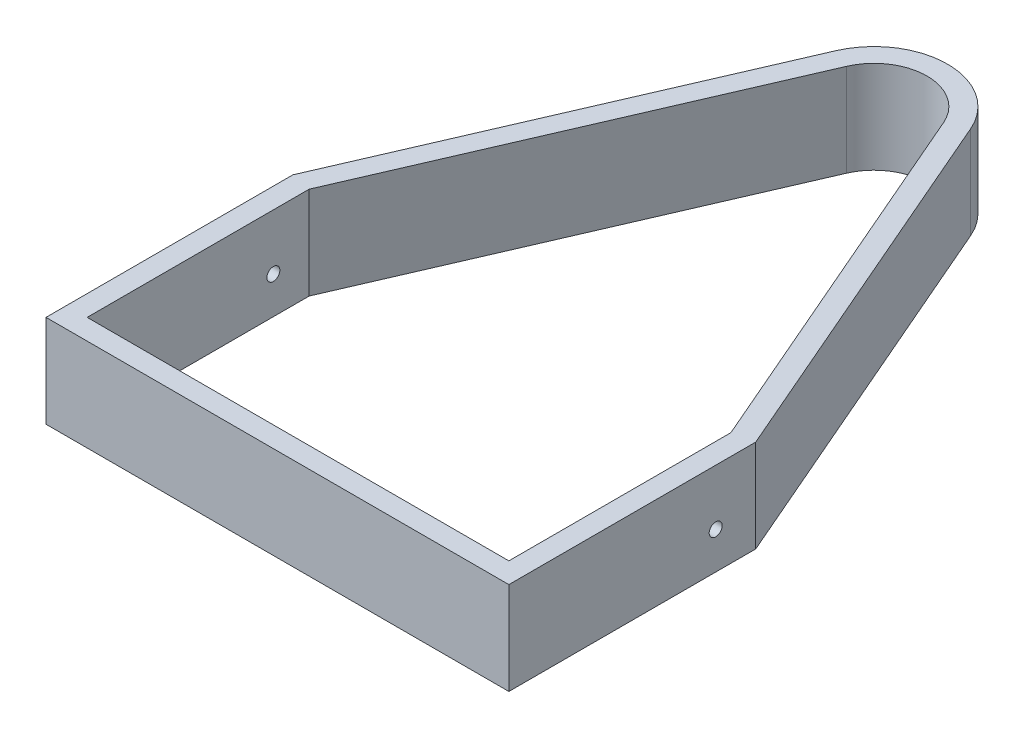
SolidWorks part; units mm, degrees
ref_plane "Front Plane" through (0, 0, 0) normal (0, 0, 1) x (1, 0, 0)
ref_plane "Top Plane" through (0, 0, 0) normal (0, 1, 0) x (1, 0, 0)
ref_plane "Right Plane" through (0, 0, 0) normal (1, 0, 0) x (0, 0, -1)
sketch "Sketch1" plane through (0, 0, 0) normal (0, 1, 0) x (1, 0, 0)
  line L0 (-71.4375, 0) -> (71.4375, 0)
  line L1 (-71.4375, 19.05) -> (71.4375, 19.05) construction
  line L2 (-71.4375, 0) -> (-71.4375, 76.2)
  line L3 (-71.4375, 19.05) -> (0, 184.15) construction
  line L8 (0, 184.15) -> (71.4375, 19.05) construction
  line L13 (71.4375, 0) -> (71.4375, 76.2)
  line L14 (-71.4375, 76.2) -> (-20.8288, 193.1624)
  line L15 (20.8288, 193.1624) -> (71.4375, 76.2)
  line L16 (-65.0875, 6.35) -> (-65.0875, 74.8851)
  line L17 (-65.0875, 74.8851) -> (-15.0009, 190.6408)
  line L18 (15.0009, 190.6408) -> (65.0875, 74.8851)
  line L19 (65.0875, 6.35) -> (65.0875, 74.8851)
  line L20 (-65.0875, 6.35) -> (65.0875, 6.35)
  arc A0 (-20.8288, 193.1624) -> (20.8288, 193.1624) centre (0, 184.15) cw
  arc A2 (-15.0009, 190.6408) -> (15.0009, 190.6408) centre (0, 184.15) cw
  point P4 (0, 0)
  dimension "D1" = 142.875
  dimension "D2" = 165.1
  dimension "D3" = 19.05
  dimension "D4" = 76.2
  dimension "D6" = 6.35
extrude "Boss-Extrude1" add sketch "Sketch1" along normal blind 28.575
sketch "Sketch2" plane through (0, 0, 0) normal (1, 0, 0) x (0, 0, -1)
  line L4 (74.8851, 28.575) -> (74.8851, 0) construction
  line L5 (0, 0) -> (76.2, 0) construction
  circle A0 centre (63.8361, 11.43) radius 11.049 construction
  circle A1 centre (63.8361, 11.43) radius 2
  dimension "D1" = 22.098
  dimension "D2" = 4
  dimension "D3" = 11.43
extrude "Cut-Extrude1" cut sketch "Sketch2" against normal up to next from surface starting at face at (-65.0875, 14.2875, -40.6176)
extrude "Cut-Extrude3" cut sketch "Sketch2<2>" along normal up to next from surface starting at face at (65.0875, 14.2875, -40.6176)
sketch "Sketch2<2>" plane through (0, 0, 0) normal (1, 0, 0) x (0, 0, -1) same geometry as "Sketch2"
